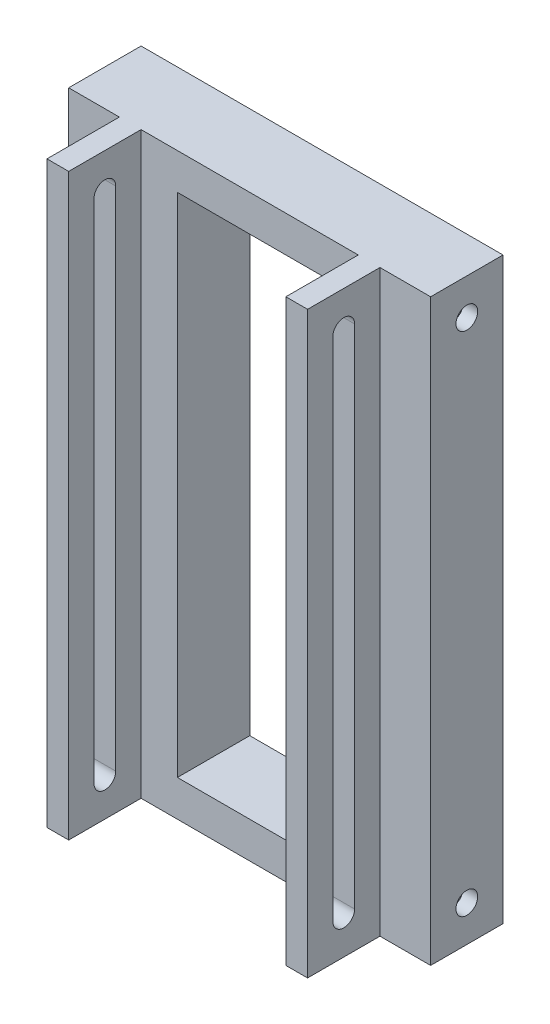
SolidWorks part; units mm, degrees
ref_plane "Plan de face" through (0, 0, 0) normal (0, 0, 1) x (1, 0, 0)
ref_plane "Plan de dessus" through (0, 0, 0) normal (0, 1, 0) x (1, 0, 0)
ref_plane "Plan de droite" through (0, 0, 0) normal (1, 0, 0) x (0, 0, -1)
sketch "Esquisse1" plane through (0, 0, 0) normal (0, 0, 1) x (1, 0, 0)
  line L0 (-13.5721, 32.3533) -> (-13.5721, -47.6467)
  line L1 (-20.5721, 32.3533) -> (29.4279, 32.3533)
  line L2 (-20.5721, 32.3533) -> (-20.5721, -47.6467)
  line L3 (-20.5721, -47.6467) -> (29.4279, -47.6467)
  line L4 (29.4279, 32.3533) -> (29.4279, -47.6467)
  line L5 (-10.5721, 32.3533) -> (-10.5721, -47.6467)
  line L6 (19.4279, 32.3533) -> (19.4279, -47.6467)
  line L7 (22.4279, 32.3533) -> (22.4279, -47.6467)
  line L8 (-13.5721, 15.6998) -> (-10.5721, 15.6998) construction
  line L9 (-13.5721, 15.6998) -> (-20.5721, 15.6998) construction
  line L10 (-10.5721, 15.6998) -> (-5.5544, 15.6998) construction
  line L11 (19.4279, 15.6998) -> (22.4279, 15.6998) construction
  line L12 (22.4279, 15.6998) -> (29.4279, 15.6998) construction
  line L13 (-5.5544, 15.6998) -> (14.4102, 15.6998) construction
  line L14 (-5.5544, 27.3533) -> (14.4456, 27.3533)
  line L15 (-5.5544, 27.3533) -> (-5.5544, -42.6467)
  line L16 (-5.5544, -42.6467) -> (14.4456, -42.6467)
  line L17 (14.4456, 27.3533) -> (14.4456, -42.6467)
  line L18 (14.4102, 15.6998) -> (19.4279, 15.6998) construction
  line L19 (4.4279, 32.3533) -> (4.4279, 27.3533) construction
  line L20 (4.4279, 27.3533) -> (4.4279, -42.6467) construction
  line L21 (4.4279, -42.6467) -> (4.4279, -47.6467) construction
  dimension "D1" = 50
  dimension "D2" = 30
  dimension "D3" = 3
  dimension "D4" = 80
  dimension "D5" = 5
  dimension "D6" = 20
extrude "Boss.-Extru.1" add sketch "Esquisse1" along normal blind 10 contours L6 L1 L5 L3 L14 L17 L16 L15 | L2 L3 L0 L1 | L1 L7 L3 L4 region at (-17.0721, -7.6467, 0) region at (4.4279, 31.4989, 0) region at (25.9279, -7.6467, 0)
extrude "Boss.-Extru.2" add sketch "Esquisse1<4>" along normal blind 20 contours L5 L1 L0 L3 | L7 L1 L6 L3 region at (-12.0721, -7.6467, 0) region at (20.9279, -7.6467, 0)
sketch "Esquisse1<4>" plane through (0, 0, 0) normal (0, 0, 1) x (1, 0, 0) same geometry as "Esquisse1"
sketch "Esquisse2" plane through (22.4279, 0, 0) normal (1, 0, 0) x (0, 0, -1)
  line L0 (-20, 27.3533) -> (-15, 27.3533) construction
  line L2 (-20, 32.3533) -> (-20, -47.6467) construction
  line L3 (-15, 27.3533) -> (-10, 27.3533) construction
  line L5 (-10, 32.3533) -> (-10, -47.6467) construction
  line L7 (-15, 32.3533) -> (-15, 27.3533) construction
  line L9 (-20, 32.3533) -> (-10, 32.3533) construction
  line L10 (-15, 27.3533) -> (-15, -42.6467) construction
  line L11 (-15, -42.6467) -> (-15, -47.6467) construction
  line L12 (-20, -47.6467) -> (-10, -47.6467) construction
  line L13 (-20, -42.6467) -> (-15, -42.6467) construction
  line L14 (-15, -42.6467) -> (-10, -42.6467) construction
  line L15 (-10, 32.3533) -> (-10, -47.6467) construction
  line L16 (-16.5, -42.6467) -> (-16.5, 27.3533)
  line L17 (-13.5, 27.3533) -> (-13.5, -42.6467)
  arc A0 (-16.5, 27.3533) -> (-13.5, 27.3533) centre (-15, 27.3533) cw
  arc A1 (-13.5, -42.6467) -> (-16.5, -42.6467) centre (-15, -42.6467) cw
  dimension "D1" = 1.5
  dimension "D2" = 5
extrude "Enlèv. mat.-Extru.1" cut sketch "Esquisse2" against normal through all
sketch "Esquisse3" plane through (-20.5721, 0, 0) normal (-1, 0, 0) x (0, 0, 1)
  line L0 (5, 32.3533) -> (5, 27.3533) construction
  line L1 (10, 32.3533) -> (0, 32.3533) construction
  line L2 (5, 27.3533) -> (5, -42.6467) construction
  line L3 (5, -42.6467) -> (5, -47.6467) construction
  line L4 (10, -47.6467) -> (0, -47.6467) construction
  line L5 (10, 27.3533) -> (5, 27.3533) construction
  line L6 (10, 32.3533) -> (10, -47.6467) construction
  line L7 (5, 27.3533) -> (0, 27.3533) construction
  line L8 (0, 32.3533) -> (0, -47.6467) construction
  line L9 (10, -42.6467) -> (5, -42.6467) construction
  line L10 (5, -42.6467) -> (0, -42.6467) construction
  circle A0 centre (5, 27.3533) radius 1.5
  circle A1 centre (5, -42.6467) radius 1.5
  dimension "D2" = 3
  dimension "D1" = 5
extrude "Enlèv. mat.-Extru.2" cut sketch "Esquisse3" against normal blind 2 contours A0 | A1
sketch "Esquisse4" plane through (29.4279, 0, 0) normal (1, 0, 0) x (0, 0, -1)
  circle A0 centre (-5, -42.6467) radius 1.5
  circle A1 centre (-5, 27.3533) radius 1.5
  circle A2 centre (-5, -42.6467) radius 1.5 construction
  circle A3 centre (-5, 27.3533) radius 1.5 construction
extrude "Enlèv. mat.-Extru.3" cut sketch "Esquisse4" against normal blind 2 contours A1 | A0
